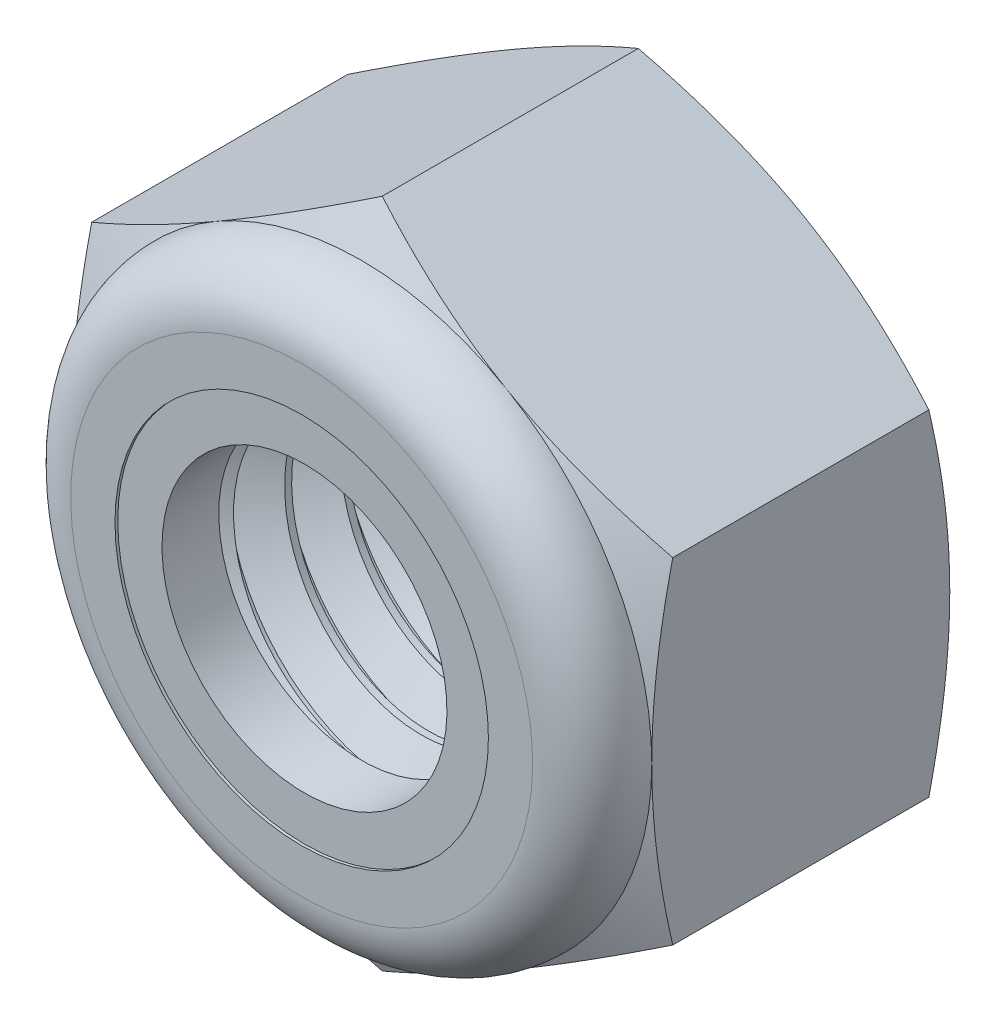
SolidWorks part; units mm, degrees
ref_plane "Front Plane" through (0, 0, 0) normal (0, 0, 1) x (1, 0, 0)
ref_plane "Top Plane" through (0, 0, 0) normal (0, 1, 0) x (1, 0, 0)
ref_plane "Right Plane" through (0, 0, 0) normal (1, 0, 0) x (0, 0, -1)
sketch "Sketch1" plane through (0, 0, 0) normal (0, 0, 1) x (1, 0, 0)
  line L1 (0, 7.5056) -> (-6.5, 3.7528)
  line L2 (-6.5, 3.7528) -> (-6.5, -3.7528)
  line L3 (-6.5, -3.7528) -> (0, -7.5056)
  line L4 (0, -7.5056) -> (6.5, -3.7528)
  line L5 (6.5, -3.7528) -> (6.5, 3.7528)
  line L6 (6.5, 3.7528) -> (0, 7.5056)
  circle A0 centre (0, 0) radius 6.5 construction
  circle A1 centre (0, 0) radius 4
  point P10 (0, -4)
  point P11 (0, 4)
  point P12 (0, 6.5)
  dimension "Thread Size" = 8
  dimension "Width" = 13
sketch "Sketch2" plane through (0, 0, 0) normal (1, 0, 0) x (0, 0, -1)
  line L0 (4, 0) -> (-4, 0) construction
  line L1 (-4, 4) -> (4, 4) construction
  line L2 (-3.9375, -4.1774) -> (-5.27, -4.1774) construction
  line L3 (-5.1719, 4.1353) -> (-3.9219, 4.1353) construction
  line L4 (-3.9219, 4.1353) -> (-4.5469, 3.0528) construction
  line L5 (-4.5469, 3.0528) -> (-5.1719, 4.1353) construction
  line L6 (-5.0938, 4) -> (-4, 4) construction
  line L7 (-4.625, 3.1881) -> (-4.4688, 3.1881) construction
  line L8 (-4.5469, 3.1881) -> (-4.5469, 3.0528) construction
  line L9 (-4.5469, 4) -> (-4.5469, 4.1353) construction
  line L10 (-3.9609, 4.0677) -> (-5.1328, 4.0677)
  line L11 (-5.1328, 4.0677) -> (-4.625, 3.1881)
  line L12 (-4.625, 3.1881) -> (-4.4688, 3.1881)
  line L13 (-4.4688, 3.1881) -> (-3.9609, 4.0677)
  line L14 (4, 0) -> (5.27, 0)
  line L15 (5.27, 0) -> (5.27, 8.7756)
  line L16 (0, 8.7756) -> (0, 7.5056) construction
  line L17 (0, 7.5056) -> (0, 3.7528) construction
  line L18 (4, 6.5) -> (-2.6667, 6.5) construction
  line L19 (-4.625, -3.1881) -> (-4.4688, -3.1881) construction
  line L20 (4, 6.5) -> (4, 0)
  line L21 (3.5311, 7.5056) -> (-2.1978, 7.5056)
  line L22 (4, 6.5) -> (3.5311, 7.5056)
  line L23 (-4, 0) -> (-4, 5.1667) construction
  line L24 (-2.6667, 6.5) -> (-2.1978, 7.5056)
  line L25 (5.27, 8.7756) -> (-5.27, 8.7756)
  line L26 (-4, 5.1667) -> (-5.27, 5.1667)
  line L27 (-5.27, 5.1667) -> (-5.27, 8.7756)
  line L28 (-3.9375, 5.1667) -> (-3.9375, 3.1881) construction
  line L29 (-3.9375, 4.1774) -> (-5.27, 4.1774)
  line L30 (-5.27, 4.1774) -> (-5.27, 0)
  line L31 (-5.27, 0) -> (-2.6667, 0)
  line L32 (-2.6667, 0) -> (-2.6667, 6.4375)
  line L33 (-3.9375, 4.1774) -> (-3.9375, 5.1667)
  arc A0 (-2.6667, 6.5) -> (-4, 5.1667) centre (-2.6667, 5.1667) ccw
  arc A1 (-2.6667, 6.4375) -> (-3.9375, 5.1667) centre (-2.6667, 5.1667) ccw
  point P4 (0, 0)
  point P18 (-4.5469, 4.0677)
  point P22 (-4.5469, 4.0677)
  point P33 (0, 7.5056)
  point P48 (-5.27, -4.1774)
  point P51 (-4.625, -3.1881)
  dimension "Height" = 8
  dimension "Pitch" = 1.25
  dimension "D1" = 0.1562
  dimension "D2" = 1.27
  dimension "D3" = 25
  dimension "D4" = 1.3333
  dimension "D5" = 25
  dimension "D6" = 0.0625
sketch "Sketch3" plane through (0, 0, 0) normal (0, 0, 1) x (1, 0, 0)
  line L0 (0, -7.5056) -> (6.5, -3.7528) construction
  line L1 (6.5, -3.7528) -> (6.5, 3.7528) construction
  line L2 (6.5, 3.7528) -> (0, 7.5056) construction
  line L3 (0, 7.5056) -> (-6.5, 3.7528) construction
  line L4 (-6.5, 3.7528) -> (-6.5, -3.7528) construction
  line L5 (-6.5, -3.7528) -> (0, -7.5056) construction
  line L6 (0, -7.5056) -> (6.5, -3.7528)
  line L7 (6.5, -3.7528) -> (6.5, 3.7528)
  line L8 (6.5, 3.7528) -> (0, 7.5056)
  line L9 (0, 7.5056) -> (-6.5, 3.7528)
  line L10 (-6.5, 3.7528) -> (-6.5, -3.7528)
  line L11 (-6.5, -3.7528) -> (0, -7.5056)
  circle A0 centre (0, 0) radius 4 construction
  circle A1 centre (0, 0) radius 4
extrude "Boss-Extrude1" add sketch "Sketch3" along normal mid plane 8
sketch "Sketch4" plane through (0, 0, 0) normal (1, 0, 0) x (0, 0, -1)
  line L0 (5.27, 8.7756) -> (-5.27, 8.7756) construction
  line L1 (-5.27, 5.1667) -> (-5.27, 8.7756) construction
  line L2 (-4, 5.1667) -> (-5.27, 5.1667) construction
  line L3 (-2.6667, 6.5) -> (-2.1978, 7.5056) construction
  line L4 (3.5311, 7.5056) -> (-2.1978, 7.5056) construction
  line L5 (4, 6.5) -> (3.5311, 7.5056) construction
  line L6 (4, 6.5) -> (4, 0) construction
  line L7 (4, 0) -> (5.27, 0) construction
  line L8 (5.27, 0) -> (5.27, 8.7756) construction
  line L9 (-5.27, 4.1774) -> (-5.27, 0) construction
  line L10 (-5.27, 0) -> (-2.6667, 0) construction
  line L11 (-2.6667, 0) -> (-2.6667, 6.4375) construction
  line L12 (-3.9375, 4.1774) -> (-3.9375, 5.1667) construction
  line L13 (-3.9375, 4.1774) -> (-5.27, 4.1774) construction
  line L14 (5.27, 8.7756) -> (-5.27, 8.7756)
  line L15 (-5.27, 5.1667) -> (-5.27, 8.7756)
  line L16 (-4, 5.1667) -> (-5.27, 5.1667)
  line L17 (-2.6667, 6.5) -> (-2.1978, 7.5056)
  line L18 (3.5311, 7.5056) -> (-2.1978, 7.5056)
  line L19 (4, 6.5) -> (3.5311, 7.5056)
  line L20 (4, 6.5) -> (4, 0)
  line L21 (4, 0) -> (5.27, 0)
  line L22 (5.27, 0) -> (5.27, 8.7756)
  line L23 (-5.27, 4.1774) -> (-5.27, 0)
  line L24 (-5.27, 0) -> (-2.6667, 0)
  line L25 (-2.6667, 0) -> (-2.6667, 6.4375)
  line L26 (-3.9375, 4.1774) -> (-3.9375, 5.1667)
  line L27 (-3.9375, 4.1774) -> (-5.27, 4.1774)
  arc A0 (-2.6667, 6.5) -> (-4, 5.1667) centre (-2.6667, 5.1667) ccw construction
  arc A1 (-2.6667, 6.4375) -> (-3.9375, 5.1667) centre (-2.6667, 5.1667) ccw construction
  arc A2 (-2.6667, 6.5) -> (-4, 5.1667) centre (-2.6667, 5.1667) ccw
  arc A3 (-2.6667, 6.4375) -> (-3.9375, 5.1667) centre (-2.6667, 5.1667) ccw
revolve "Cut-Revolve1" cut sketch "Sketch4" angle 360 about L0
sketch "Sketch5" plane through (0, 0, 0) normal (1, 0, 0) x (0, 0, -1)
  line L0 (-3.9375, 5.1667) -> (-3.9375, 3.1881) construction
  line L1 (-2.6667, 0) -> (-2.6667, 6.4375) construction
  line L2 (-3.9375, 5.1667) -> (-3.9375, 3.1881)
  line L3 (-2.6667, 3.1881) -> (-2.6667, 6.4375)
  line L4 (-3.9375, 3.1881) -> (-2.6667, 3.1881)
  arc A0 (-2.6667, 6.4375) -> (-3.9375, 5.1667) centre (-2.6667, 5.1667) ccw construction
  arc A1 (-2.6667, 6.4375) -> (-3.9375, 5.1667) centre (-2.6667, 5.1667) ccw
revolve "Revolve1" add sketch "Sketch5" angle 360 about L0
sketch "Sketch6" plane through (0, 0, 4) normal (0, 0, 1) x (1, 0, 0)
  circle A0 centre (0, 0) radius 4 construction
  circle A1 centre (0, 0) radius 4
curve "Helix/Spiral1" pitch 1.25 height 9.25 radius 4 centre (0, 0, 4) axis (0, 0, -1) start towards (0, 1, 0)
sketch "Sketch7" plane through (0, 0, 0) normal (1, 0, 0) x (0, 0, -1)
  line L0 (-5.1328, 4.0677) -> (-4.625, 3.1881) construction
  line L1 (-4.625, 3.1881) -> (-4.4688, 3.1881) construction
  line L2 (-4.4688, 3.1881) -> (-3.9609, 4.0677) construction
  line L3 (-3.9609, 4.0677) -> (-5.1328, 4.0677) construction
  line L4 (-5.1328, 4.0677) -> (-4.625, 3.1881)
  line L5 (-4.625, 3.1881) -> (-4.4688, 3.1881)
  line L6 (-4.4688, 3.1881) -> (-3.9609, 4.0677)
  line L7 (-3.9609, 4.0677) -> (-5.1328, 4.0677)
sweep "Sweep1" add profiles "Sketch7" path "Helix/Spiral1"
sketch "Sketch8" plane through (0, 0, -4) normal (0, 0, -1) x (-1, 0, 0)
  circle A2 centre (0, 0) radius 4.0677
  point P2 (0, 4.0677)
extrude "Cut-Extrude1" cut sketch "Sketch8" along normal through all and the other way through all draft 60
sketch "Sketch9" plane through (0, 0, 2.6667) normal (0, 0, 1) x (1, 0, 0)
  circle A2 centre (0, 0) radius 4.0677
  circle A3 centre (0, 0) radius 3.1881 construction
  point P2 (0, 4.0677)
  point P4 (0, 3.1881)
extrude "Cut-Extrude2" cut sketch "Sketch9" along normal through all and the other way through all draft 60
equation "\"D1@Sketch2\" = \"Pitch@Sketch2\" / 8"
equation "\"D4@Sketch2\"=\"Height@Sketch2\"/6"
equation "\"D1@Boss-Extrude1\"=\"Height@Sketch2\""
equation "\"D3@Helix/Spiral1\"=\"Height@Sketch2\"+\"Pitch@Sketch2\""
equation "\"D4@Helix/Spiral1\"=\"Pitch@Sketch2\""
equation "\"D6@Sketch2\"=\"Pitch@Sketch2\"*0.05"
